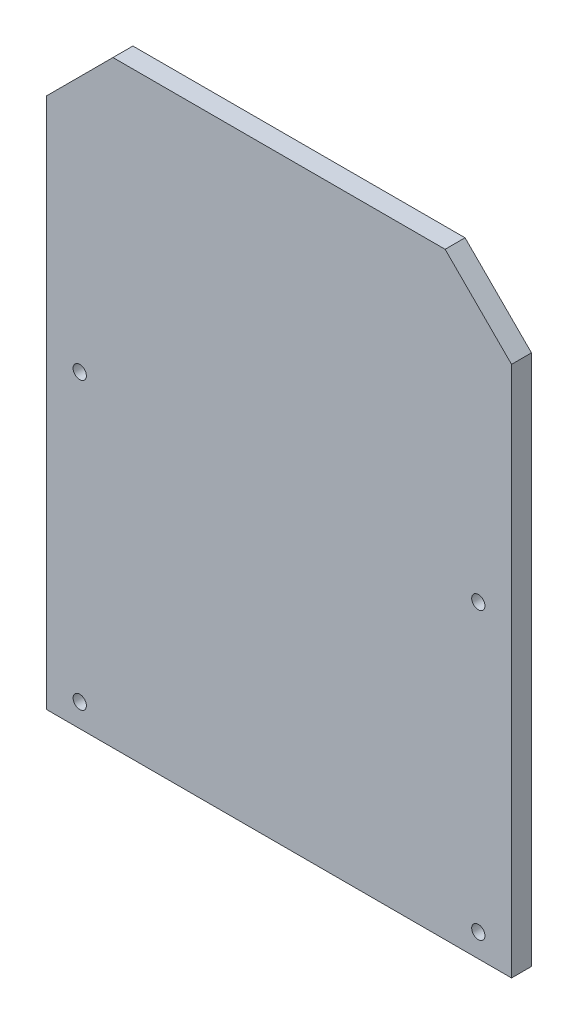
SolidWorks part; units mm, degrees
ref_plane "Alzado" through (0, 0, 0) normal (0, 0, 1) x (1, 0, 0)
ref_plane "Planta" through (0, 0, 0) normal (0, 1, 0) x (1, 0, 0)
ref_plane "Vista lateral" through (0, 0, 0) normal (1, 0, 0) x (0, 0, -1)
sketch "Croquis1" plane through (0, 0, 0) normal (0, 0, 1) x (1, 0, 0)
  line L5 (-30.0455, 36.9284) -> (39.9545, 36.9284)
  line L6 (-30.0455, 36.9284) -> (-30.0455, -53.0716)
  line L7 (-30.0455, -53.0716) -> (39.9545, -53.0716)
  line L8 (39.9545, 36.9284) -> (39.9545, -53.0716)
  dimension "D1" = 70
  dimension "D2" = 90
extrude "Saliente-Extruir1" add sketch "Croquis1" along normal blind 3
sketch "Croquis2" plane through (0, 0, 0) normal (0, 0, -1) x (-1, 0, 0)
  line L0 (-34.9545, -49.5716) -> (-39.9545, -49.5716) construction
  line L1 (-39.9545, -53.0716) -> (-39.9545, 36.9284) construction
  line L2 (25.0455, -49.5716) -> (30.0455, -49.5716) construction
  line L3 (30.0455, 36.9284) -> (30.0455, -53.0716) construction
  line L4 (25.0455, -49.5716) -> (25.0455, -53.0716) construction
  line L5 (30.0455, -53.0716) -> (-39.9545, -53.0716) construction
  line L6 (-34.9545, -49.5716) -> (-34.9545, -53.0716) construction
  line L7 (-34.9545, -6.5716) -> (-34.9545, -49.5716) construction
  circle A0 centre (-34.9545, -49.5716) radius 1
  circle A1 centre (25.0455, -49.5716) radius 1
  circle A2 centre (-34.9545, -6.5716) radius 1
  circle A3 centre (25.0455, -6.5716) radius 1
extrude "Cortar-Extruir1" cut sketch "Croquis2" against normal blind 3
fillet "Chaflán1" radius 10 1 edges at (39.9545, 36.9284, 1.5) type face fillet profile chamfer first side face at (39.9545, -8.0716, 1.5) second side face at (4.9545, 36.9284, 1.5)
fillet "Chaflán2" radius 10 1 edges at (-30.0455, 36.9284, 1.5) type face fillet profile chamfer first side face at (-0.0455, 36.9284, 1.5) second side face at (-30.0455, -8.0716, 1.5)
